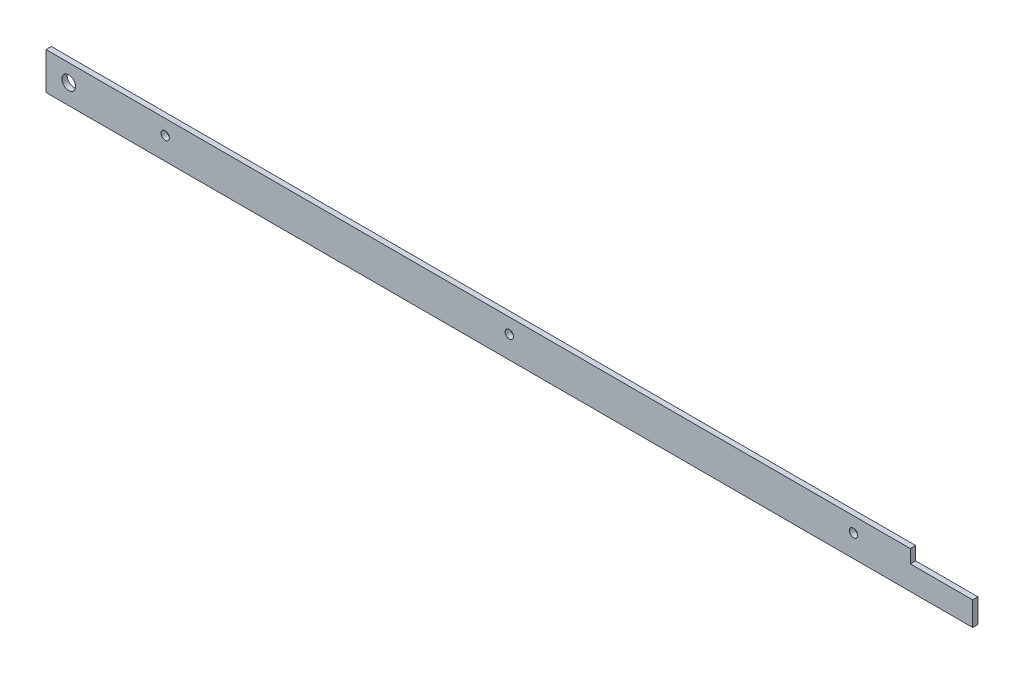
SolidWorks part; units mm, degrees
ref_plane "Front Plane" through (0, 0, 0) normal (0, 0, 1) x (1, 0, 0)
ref_plane "Top Plane" through (0, 0, 0) normal (0, 1, 0) x (1, 0, 0)
ref_plane "Right Plane" through (0, 0, 0) normal (1, 0, 0) x (0, 0, -1)
sketch "Sketch1" plane through (0, 0, 0) normal (0, 0, 1) x (1, 0, 0)
  line L0 (515.86, 17.392) -> (0, 17.392) construction
  line L5 (515.86, 41.507) -> (515.86, -0.373) construction
  line L6 (553.1, 9.447) -> (515.86, 9.447) construction
  line L9 (0, -4.833) -> (553.1, -4.833)
  line L10 (553.1, 9.447) -> (553.1, -4.833)
  line L11 (0, -4.833) -> (0, 45.967) construction
  line L12 (516.014, 17.392) -> (0, 17.392)
  line L13 (0, -4.833) -> (0, 17.392)
  line L14 (516.014, 17.392) -> (515.86, 17.392)
  line L15 (515.86, 9.447) -> (515.86, 17.392)
  line L16 (0, 20.567) -> (553.1, 20.567) construction
  line L17 (515.86, 9.447) -> (553.1, 9.447)
  line L19 (0, 20.567) -> (457.2, 20.567) construction
  circle A0 centre (71.12, 8.5095) radius 2.4892 construction
  circle A1 centre (13.54, 34.107) radius 13.54 construction
  circle A2 centre (13.54, 34.107) radius 4.0635 construction
  circle A6 centre (71.12, 8.5095) radius 2.4892
  circle A7 centre (276.55, 8.5095) radius 2.4892
  circle A8 centre (481.98, 8.5095) radius 2.4892
  circle A9 centre (13.54, 7.027) radius 4.0635
  point P6 (0, 0)
  point P11 (515.86, 9.447)
  point P33 (276.55, 8.5095)
  point P35 (481.98, 8.5095)
  point P39 (0, 0)
  dimension "D1" = 8.127
extrude "Boss-Extrude1" add sketch "Sketch1" along normal blind 3.175 contours L17 L15 L14 L12 L13 L9 L10 A8 A7 A6 region at (271.2776, 6.0875, 0)
